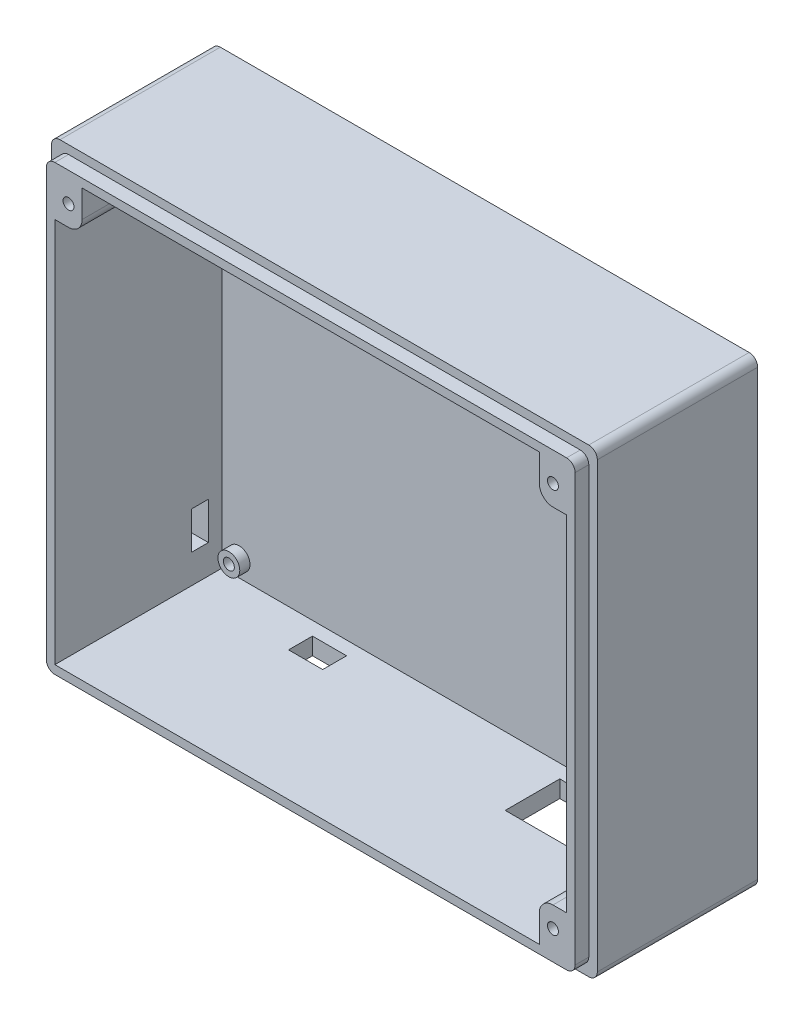
SolidWorks part; units mm, degrees
ref_plane "Plan de face" through (0, 0, 0) normal (0, 0, 1) x (1, 0, 0)
ref_plane "Plan de dessus" through (0, 0, 0) normal (0, 1, 0) x (1, 0, 0)
ref_plane "Plan de droite" through (0, 0, 0) normal (1, 0, 0) x (0, 0, -1)
sketch "Esquisse1" plane through (0, 0, 0) normal (0, 0, 1) x (1, 0, 0)
  line L0 (0, 67.5) -> (160, 67.5) construction
  line L1 (0, 0) -> (160, 0)
  line L2 (0, 0) -> (0, 135)
  line L3 (0, 135) -> (160, 135)
  line L4 (160, 0) -> (160, 135)
  line L5 (80, 135) -> (80, 0) construction
  line L6 (155, 5) -> (147, 17) construction
  line L7 (5, 5) -> (155, 5)
  line L8 (5, 5) -> (5, 130)
  line L9 (5, 130) -> (155, 130)
  line L10 (155, 5) -> (155, 130)
  line L11 (5, 5) -> (155, 130) construction
  line L12 (5, 130) -> (155, 5) construction
  line L13 (2.5, 2.5) -> (157.5, 2.5)
  line L14 (2.5, 2.5) -> (2.5, 132.5)
  line L15 (2.5, 132.5) -> (157.5, 132.5)
  line L16 (157.5, 2.5) -> (157.5, 132.5)
  line L17 (2.5, 2.5) -> (157.5, 132.5) construction
  line L18 (2.5, 132.5) -> (157.5, 2.5) construction
  line L19 (155, 5) -> (147, 5)
  line L20 (155, 5) -> (155, 17)
  line L21 (155, 17) -> (147, 17)
  line L22 (147, 5) -> (147, 17)
  line L23 (147, 5) -> (155, 17) construction
  line L24 (147, 130) -> (155, 118) construction
  line L25 (155, 130) -> (147, 130)
  line L26 (155, 130) -> (155, 118)
  line L27 (155, 118) -> (147, 118)
  line L28 (147, 130) -> (147, 118)
  line L29 (5, 130) -> (13, 130)
  line L30 (5, 130) -> (5, 118)
  line L31 (5, 118) -> (13, 118)
  line L32 (13, 130) -> (13, 118)
  line L33 (155, 130) -> (147, 118) construction
  line L34 (5, 130) -> (13, 118) construction
  line L35 (13, 130) -> (5, 118) construction
  circle A0 centre (10, 10) radius 1.6
  circle A1 centre (10, 10) radius 3.2
  circle A2 centre (142, 10) radius 1.6
  circle A3 centre (142, 10) radius 3.2
  circle A4 centre (142, 112) radius 1.6
  circle A5 centre (142, 112) radius 3.2
  circle A6 centre (10, 112) radius 1.6
  circle A7 centre (10, 112) radius 3.2
  arc A8 (157.5, 135) -> (160, 132.5) centre (157.5, 132.5) cw
  arc A9 (155, 132.5) -> (157.5, 130) centre (155, 130) cw
  arc A10 (157.5, 5) -> (155, 2.5) centre (155, 5) cw
  arc A11 (157.5, 0) -> (160, 2.5) centre (157.5, 2.5) ccw
  arc A12 (2.5, 5) -> (5, 2.5) centre (5, 5) ccw
  arc A13 (0, 2.5) -> (2.5, 0) centre (2.5, 2.5) ccw
  arc A14 (5, 132.5) -> (2.5, 130) centre (5, 130) ccw
  arc A15 (2.5, 135) -> (0, 132.5) centre (2.5, 132.5) ccw
  circle A17 centre (151, 11) radius 1.6
  circle A18 centre (151, 124) radius 1.6
  circle A19 centre (9, 124) radius 1.6
  point P9 (80, 67.5)
  point P34 (80, 67.5)
  dimension "D7" = 132
  dimension "D1" = 135
  dimension "D2" = 160
  dimension "D3" = 150
  dimension "D4" = 125
  dimension "D5" = 5
  dimension "D6" = 5
  dimension "D8" = 8
  dimension "D9" = 102
  dimension "D10" = 5
  dimension "D11" = 102
  dimension "D12" = 12
  dimension "D13" = 155
  dimension "D14" = 130
  dimension "D15" = 8
  dimension "D16" = 12
  dimension "D17" = 8
  dimension "D18" = 12
extrude "Boss.-Extru.3" add sketch "Esquisse1" along normal blind 2 contours L7 L10 L9 L8 A7 A5 A3 A1 | A5 A4 | A4 | A7 A6 | A6 | A1 A0 | A3 A2 | A2 | A0 | L30 L29 L32 L31 | L26 L25 L28 L27 | L20 L19 L22 L21 region at (79.6563, 67.2498, 0) region at (6.8905, 10, 0) region at (142, 10, 0) region at (138.8905, 10, 0) region at (142, 112, 0) region at (138.8905, 112, 0) region at (10, 112, 0) region at (6.8905, 112, 0)
ref_plane "Plan1" through (5, 130, 0) normal (1, 0, 0) x (0, 0, -1)
extrude "Boss.-Extru.4" add sketch "Esquisse1<6>" along normal blind 51 contours L13 L16 L15 L14 L10 L7 L8 L9 region at (4.6627, 4.6627, 0)
sketch "Esquisse1<6>" plane through (0, 0, 0) normal (0, 0, 1) x (1, 0, 0) same geometry as "Esquisse1"
extrude "Boss.-Extru.6" add sketch "Esquisse1<8>" along normal blind 47 contours L14 L15 | L1 L4 L3 L2 L16 L13 L14 L15 | L15 L16 | L13 L16 | L14 L13 region at (2.2125, 2.2125, 0) region at (3.0584, 3.0584, 0) region at (156.9416, 3.0584, 0) region at (3.0584, 131.9416, 0) region at (156.9416, 131.9416, 0)
sketch "Esquisse1<8>" plane through (0, 0, 0) normal (0, 0, 1) x (1, 0, 0) same geometry as "Esquisse1"
extrude "Boss.-Extru.7" add sketch "Esquisse1<9>" along normal blind 5 contours A5 A4 | A7 A6 | A1 A0 | A3 A2 region at (6.8905, 10, 0) region at (138.8905, 10, 0) region at (138.8905, 112, 0) region at (6.8905, 112, 0)
sketch "Esquisse1<9>" plane through (0, 0, 0) normal (0, 0, 1) x (1, 0, 0) same geometry as "Esquisse1"
sketch "Esquisse3" plane through (0, 0, 0) normal (0, -1, 0) x (1, 0, 0)
  line L1 (108, 6) -> (126, 6)
  line L2 (108, 6) -> (108, 22)
  line L3 (108, 22) -> (126, 22)
  line L4 (126, 6) -> (126, 22)
  line L5 (108, 6) -> (126, 22) construction
  line L6 (108, 22) -> (126, 6) construction
  line L7 (35.5, 13) -> (45.5, 13)
  line L8 (35.5, 13) -> (35.5, 6)
  line L9 (35.5, 6) -> (45.5, 6)
  line L10 (45.5, 13) -> (45.5, 6)
  point P0 (117, 14)
  dimension "D1" = 31.5
  dimension "D2" = 6
  dimension "D3" = 16
  dimension "D4" = 18
  dimension "D5" = 33
  dimension "D6" = 10
  dimension "D7" = 7
  dimension "D8" = 6
extrude "Enlèv. mat.-Extru.1" cut sketch "Esquisse3" against normal blind 15
sketch "Esquisse4" plane through (0, 0, 0) normal (-1, 0, 0) x (0, 0, 1)
  line L1 (6, 24.5) -> (11, 24.5)
  line L2 (6, 24.5) -> (6, 13.5)
  line L3 (6, 13.5) -> (11, 13.5)
  line L4 (11, 24.5) -> (11, 13.5)
  line L5 (6, 24.5) -> (11, 13.5) construction
  line L6 (6, 13.5) -> (11, 24.5) construction
  point P0 (8.5, 19)
  dimension "D1" = 11
  dimension "D2" = 11
  dimension "D3" = 6
  dimension "D4" = 5
extrude "Enlèv. mat.-Extru.2" cut sketch "Esquisse4" against normal blind 15
extrude "Boss.-Extru.8" add sketch "Esquisse1<12>" along normal blind 51 contours L9 L28 L27 L10 A18 | L22 L7 L10 L21 A17 | L29 L32 L31 L30 | A19 region at (147.1442, 11, 0) region at (151, 118.1442, 0)
sketch "Esquisse1<12>" plane through (0, 0, 0) normal (0, 0, 1) x (1, 0, 0) same geometry as "Esquisse1"
fillet "Congé5" radius 4 3 edges at (147, 17, 26.5) (147, 118, 26.5) (13, 118, 26.5)
